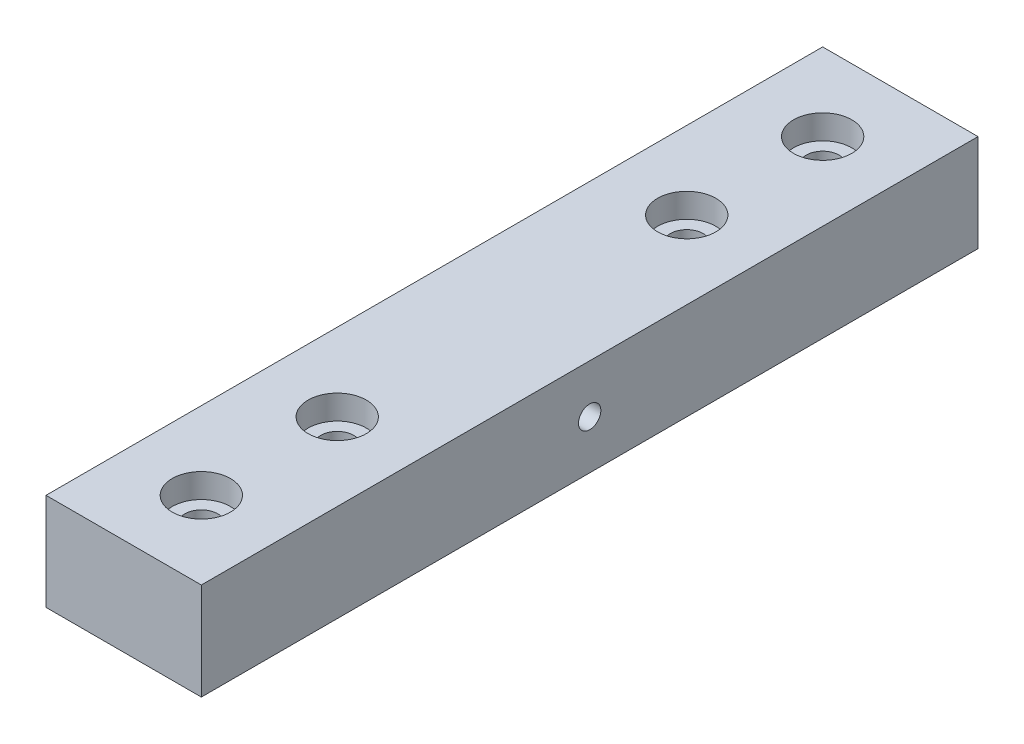
SolidWorks part; units mm, degrees
ref_plane "Ebene vorne" through (0, 0, 0) normal (0, 0, 1) x (1, 0, 0)
ref_plane "Ebene oben" through (0, 0, 0) normal (0, 1, 0) x (1, 0, 0)
ref_plane "Ebene rechts" through (0, 0, 0) normal (1, 0, 0) x (0, 0, -1)
sketch "Sketch1" plane through (0, 0, 0) normal (0, 1, 0) x (1, 0, 0)
  line L0 (0, 88.4363) -> (0, -16.8125) construction
  line L1 (-8, 80) -> (8, 80)
  line L2 (-8, 80) -> (-8, 0)
  line L3 (-8, 0) -> (8, 0)
  line L4 (8, 80) -> (8, 0)
  dimension "D1" = 16
  dimension "D2" = 80
sketch "Sketch2" plane through (0, 0, 0) normal (0, 1, 0) x (1, 0, 0)
  line L0 (0, 87.0713) -> (0, -18.1775) construction
  circle A0 centre (0, 72) radius 2.35
  circle A1 centre (0, 58) radius 2.35
  circle A2 centre (0, 22) radius 2.35
  circle A3 centre (0, 8) radius 2.35
  circle A4 centre (0, 72) radius 3
  circle A5 centre (0, 58) radius 3
  circle A6 centre (0, 22) radius 3
  circle A7 centre (0, 8) radius 3
  circle A8 centre (0, 72) radius 1.7
  circle A9 centre (0, 58) radius 1.7
  circle A10 centre (0, 22) radius 1.7
  circle A11 centre (0, 8) radius 1.7
  dimension "D3" = 4.7
  dimension "D1" = 6
  dimension "D2" = 3.4
  dimension "D4" = 14
  dimension "D5" = 14
  dimension "D6" = 50
  dimension "D7" = 8
extrude "Boss-Extrude1" add sketch "Sketch1" along normal blind 10
extrude "Cut-Extrude1" cut sketch "Sketch2" along normal blind 2.5 contours A0 | A1 | A2 | A3
extrude "Cut-Extrude2" cut sketch "Sketch2<3>" along normal through all contours A8 | A9 | A10 | A11
sketch "Sketch2<3>" plane through (0, 0, 0) normal (0, 1, 0) x (1, 0, 0) same geometry as "Sketch2"
extrude "Cut-Extrude3" cut sketch "Sketch2<4>" along normal through all from offset 7.5 contours A4 | A5 | A6 | A7
sketch "Sketch2<4>" plane through (0, 0, 0) normal (0, 1, 0) x (1, 0, 0) same geometry as "Sketch2"
sketch "Sketch3" plane through (8, 0, 0) normal (1, 0, 0) x (0, 0, -1)
  circle A0 centre (40, 5) radius 1.15
  dimension "D1" = 2.3
  dimension "D2" = 5
  dimension "D3" = 40
extrude "Cut-Extrude4" cut sketch "Sketch3" against normal through all
